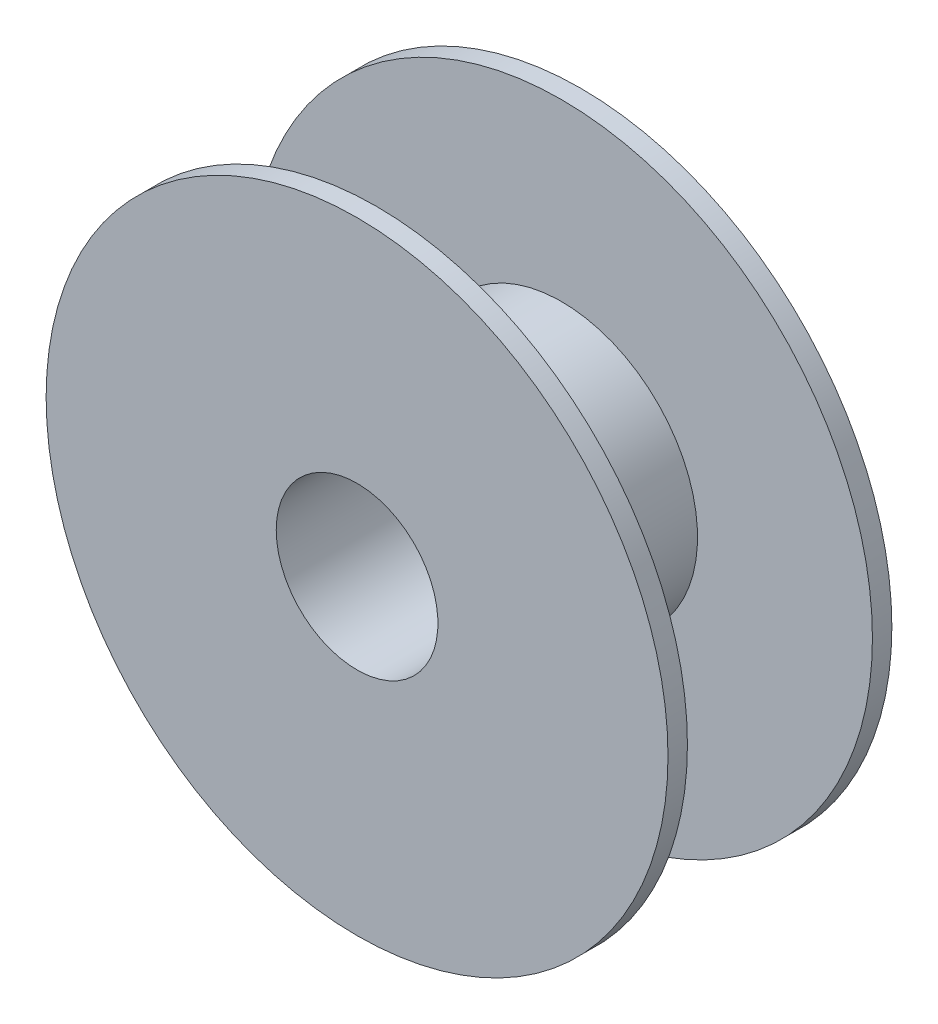
SolidWorks part; units mm, degrees
ref_plane "Front Plane" through (0, 0, 0) normal (0, 0, 1) x (1, 0, 0)
ref_plane "Top Plane" through (0, 0, 0) normal (0, 1, 0) x (1, 0, 0)
ref_plane "Right Plane" through (0, 0, 0) normal (1, 0, 0) x (0, 0, -1)
sketch "Sketch1" plane through (0, 0, 0) normal (0, 0, 1) x (1, 0, 0)
  circle A0 centre (0, 0) radius 101.6
  dimension "D1" = 203.2
extrude "Boss-Extrude1" add sketch "Sketch1" along normal blind 73.152
sketch "Sketch2" plane through (0, 0, 0) normal (0, 1, 0) x (1, 0, 0)
  line L0 (0, 0) -> (0, -73.152)
  line L1 (-101.6, -73.152) -> (101.6, -73.152) construction
ref_axis "Axis1" through (0, 0, 0) along (0, 0, 1)
sketch "Sketch3" plane through (0, 0, 0) normal (1, 0, 0) x (0, 0, -1)
  line L3 (-6.35, 101.6) -> (-66.802, 101.6)
  line L5 (0, 101.6) -> (-73.152, 101.6) construction
  line L8 (-66.802, 44.45) -> (-6.35, 44.45)
  line L9 (-6.35, 44.45) -> (-6.35, 101.6)
  line L10 (-66.802, 101.6) -> (-66.802, 44.45)
  line L11 (0, 0) -> (-73.152, 0) construction
  dimension "D1" = 44.45
revolve "Cut-Revolve2" cut sketch "Sketch3" angle 360 about L0
sketch "Sketch4" plane through (0, 0, 0) normal (0, 0, -1) x (-1, 0, 0)
  circle A0 centre (0, 0) radius 26.416
  dimension "D1" = 52.832
extrude "Cut-Extrude1" cut sketch "Sketch4" against normal blind 73.152
